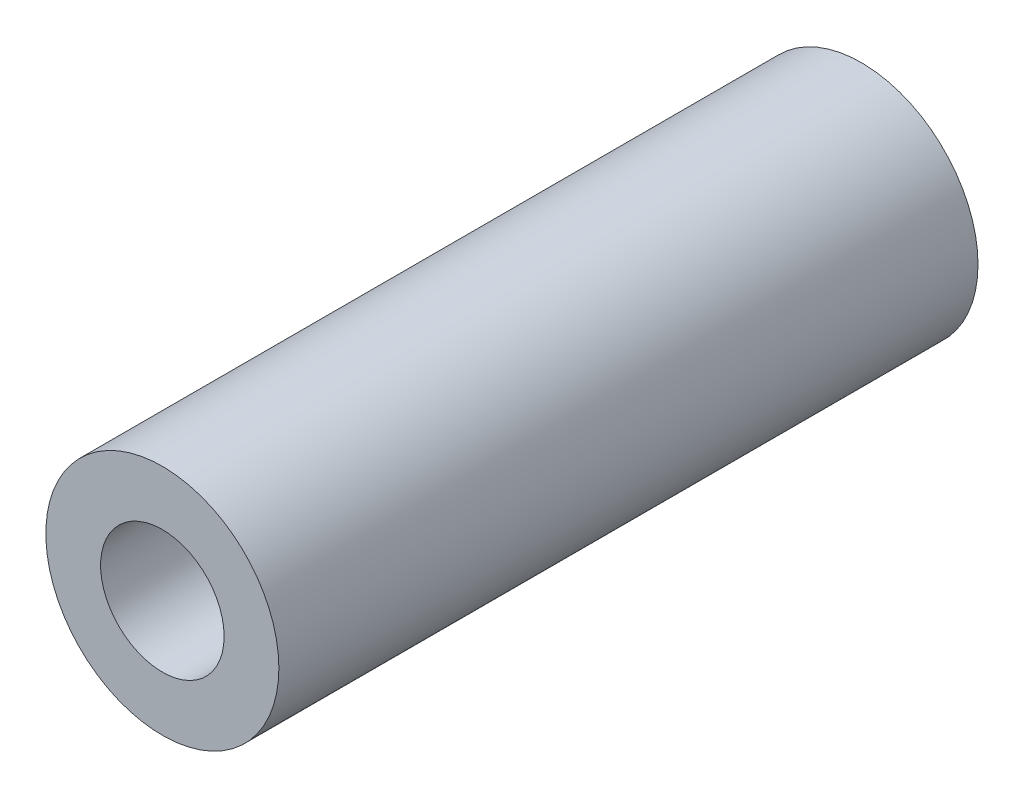
SolidWorks part; units mm, degrees
ref_plane "Front Plane" through (0, 0, 0) normal (0, 0, 1) x (1, 0, 0)
ref_plane "Top Plane" through (0, 0, 0) normal (0, 1, 0) x (1, 0, 0)
ref_plane "Right Plane" through (0, 0, 0) normal (1, 0, 0) x (0, 0, -1)
sketch "Sketch1" plane through (0, 0, 0) normal (0, 0, 1) x (1, 0, 0)
  circle A0 centre (0, 0) radius 5
  circle A1 centre (0, 0) radius 2.65
  dimension "OD" = 10
  dimension "ID" = 5.3
extrude "Extrude1" add sketch "Sketch1" along normal mid plane 30
